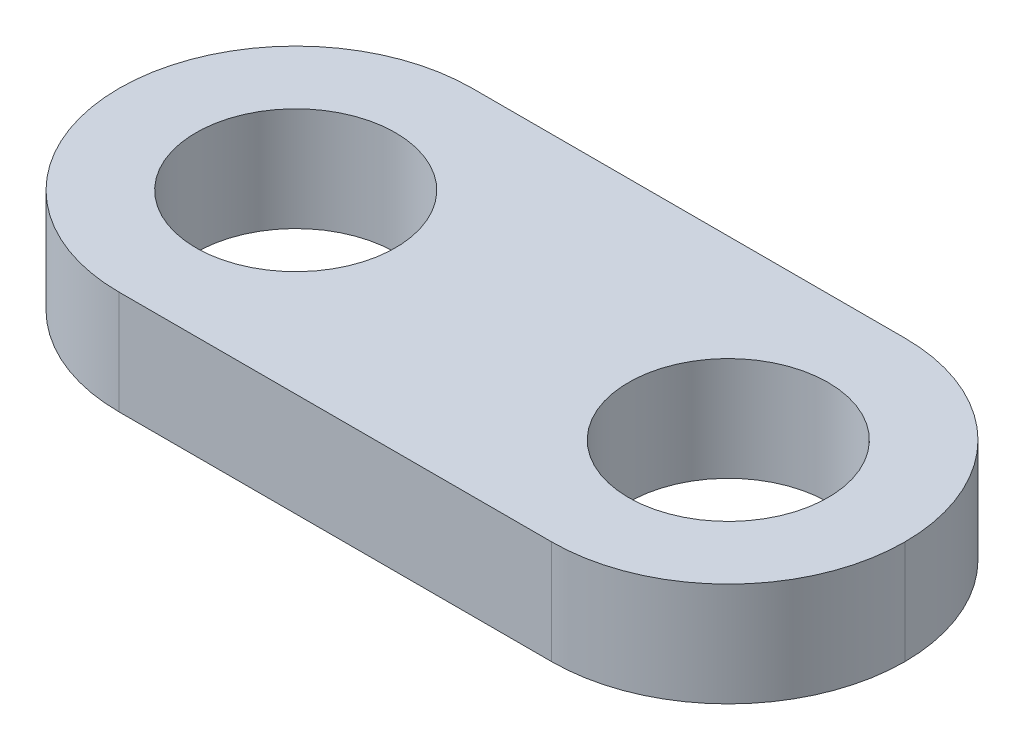
SolidWorks part; units mm, degrees
ref_plane "Front Plane" through (0, 0, 0) normal (0, 0, 1) x (1, 0, 0)
ref_plane "Top Plane" through (0, 0, 0) normal (0, 1, 0) x (1, 0, 0)
ref_plane "Right Plane" through (0, 0, 0) normal (1, 0, 0) x (0, 0, -1)
sketch "Sketch1" plane through (0, 0, 0) normal (0, 1, 0) x (1, 0, 0)
  line L1 (0, 0) -> (17.8, 0)
  line L2 (0, 0) -> (0, 8)
  line L3 (0, 8) -> (17.8, 8)
  line L4 (17.8, 0) -> (17.8, 8)
  dimension "D1" = 17.8
  dimension "D2" = 8
extrude "Boss-Extrude1" add sketch "Sketch1" along normal blind 2.35
sketch "Sketch2" plane through (0, 2.35, 0) normal (0, 1, 0) x (1, 0, 0)
  line L0 (0, 4) -> (17.8, 4) construction
  line L1 (0, 8) -> (0, 0) construction
  line L2 (17.8, 0) -> (17.8, 8) construction
  circle A0 centre (4, 4) radius 2.26
  circle A1 centre (13.8, 4) radius 2.26
  dimension "D3" = 4.52
  dimension "D1" = 4
  dimension "D2" = 4
extrude "Cut-Extrude1" cut sketch "Sketch2" against normal through all
fillet "Fillet1" radius 4 4 edges at (17.8, 1.175, 0) (0, 1.175, 0) (17.8, 1.175, -8) (0, 1.175, -8)
